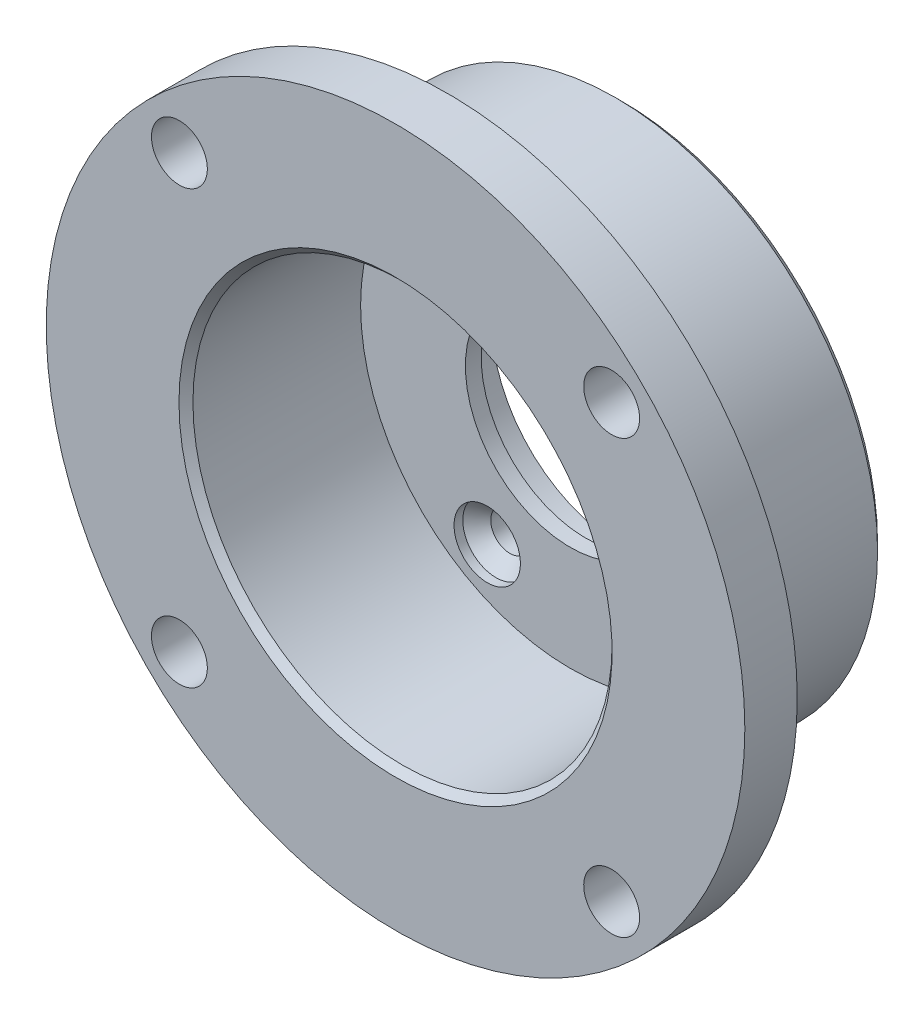
SolidWorks part; units mm, degrees
material "Литая углеродистая сталь"
ref_plane "Спереди" through (0, 0, 0) normal (0, 0, 1) x (1, 0, 0)
ref_plane "Сверху" through (0, 0, 0) normal (0, 1, 0) x (1, 0, 0)
ref_plane "Справа" through (0, 0, 0) normal (1, 0, 0) x (0, 0, -1)
sketch "Эскиз1" plane through (0, 0, 0) normal (0, 1, 0) x (1, 0, 0)
  line L0 (-20, 0) -> (-20, 3)
  line L1 (-20, 3) -> (-15, 3)
  line L2 (-15, 3) -> (-15, 13)
  line L3 (-15, 13) -> (-7.5, 13)
  line L4 (-7.5, 13) -> (-7.5, 10.9)
  line L6 (-12, 10) -> (-12, 0)
  line L7 (-12, 0) -> (-20, 0)
  line L8 (0, 0) -> (0, 50000) construction
  line L10 (-6, 10) -> (-6, 10.9)
  line L11 (-6, 10.9) -> (-7.5, 10.9)
  line L12 (-12, 10) -> (-6, 10)
  dimension "D1" = 7.5
  dimension "D2" = 15
  dimension "D3" = 12
  dimension "D4" = 3
  dimension "D5" = 3
  dimension "D6" = 20
  dimension "D7" = 13
  dimension "D10" = 0.9
  dimension "D11" = 6
revolve "Повернуть1" add sketch "Эскиз1" angle 360 about L8
sketch "Эскиз2" plane through (0, 0, -10) normal (0, 0, 1) x (1, 0, 0)
  line L0 (0, 0) -> (-12, 0) construction
  line L1 (0, 0) -> (12, 0) construction
  circle A0 centre (4.75, 8.2272) radius 1.1
  circle A3 centre (0, 0) radius 12 construction
  circle A6 centre (-4.75, -8.2272) radius 1.1
  circle A7 centre (0, 0) radius 12 construction
  point P13 (0, 0)
  dimension "D1" = 2.2
  dimension "D4" = 2.2
  dimension "D5" = 60
  dimension "D2" = 9.5
  dimension "D3" = 60
  dimension "D6" = 9.5
extrude "Вырез-Вытянуть1" cut sketch "Эскиз2" against normal up to next
pattern_circular "Круговой массив1" count 2 every 60 about axis through (0, 0, 0) along (0, 0, 1) of "Вырез-Вытянуть1"
sketch "Эскиз3" plane through (0, 0, -10) normal (0, 0, 1) x (1, 0, 0)
  circle A0 centre (4.75, 8.2272) radius 1.9
  circle A2 centre (-4.75, -8.2272) radius 1.9
  dimension "D1" = 3.8
  dimension "D2" = 3.8
extrude "Вырез-Вытянуть2" cut sketch "Эскиз3" against normal blind 0.5
pattern_circular "Круговой массив2" count 2 every 60 about axis through (0, 0, 0) along (0, 0, 1) of "Вырез-Вытянуть2"
sketch "Эскиз4" plane through (0, 0, -10.5) normal (0, 0, 1) x (1, 0, 0)
  circle A0 centre (4.75, 8.2272) radius 1.9
  dimension "D1" = 3.8
extrude "Вырез-Вытянуть3" cut sketch "Эскиз4" against normal blind 1.2 draft 45
pattern_circular "Круговой массив3" count 6 every 60 about axis through (0, 0, 0) along (0, 0, 1) of "Вырез-Вытянуть3"
sketch "Эскиз5" plane through (0, 0, 0) normal (0, 0, 1) x (1, 0, 0)
  line L0 (0, 0) -> (20, 0) construction
  circle A2 centre (0, 0) radius 12 construction
  circle A3 centre (12.3744, 12.3744) radius 1.6
  circle A4 centre (0, 0) radius 20 construction
  point P13 (-20.566, 18.6849)
  dimension "D1" = 17.5
  dimension "D2" = 3.2
  dimension "D3" = 45
extrude "Вырез-Вытянуть4" cut sketch "Эскиз5" against normal up to next
pattern_circular "Круговой массив4" count 4 over 360 about axis through (0, 0, 0) along (0, 0, 1) of "Вырез-Вытянуть4" reverse direction yes
chamfer "Фаска1" distance 0.4 angle 45 2 edges at (15, 0, -13) (12, 0, 0)
